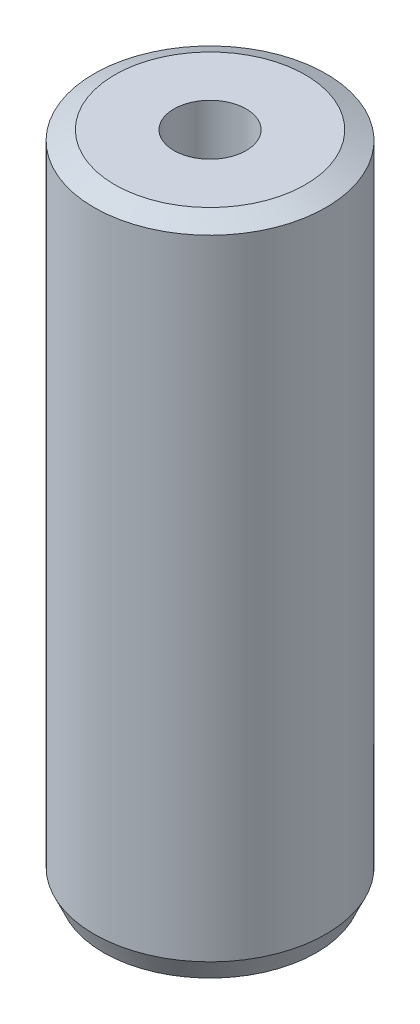
SolidWorks part; units mm, degrees
ref_plane "Front Plane" through (0, 0, 0) normal (0, 0, 1) x (1, 0, 0)
ref_plane "Top Plane" through (0, 0, 0) normal (0, 1, 0) x (1, 0, 0)
ref_plane "Right Plane" through (0, 0, 0) normal (1, 0, 0) x (0, 0, -1)
sketch "Sketch1" plane through (0, 0, 0) normal (0, 1, 0) x (1, 0, 0)
  circle A0 centre (0, 0) radius 47.5
  dimension "SHAFT_OD" = 95
extrude "Boss-Extrude1" add sketch "Sketch1" along normal blind 270.1124
sketch "Sketch2" plane through (0, 0, 0) normal (0, 1, 0) x (1, 0, 0)
  circle A0 centre (0, 0) radius 14.7958
  dimension "BORE_D" = 29.5915
extrude "Cut-Extrude1" cut sketch "Sketch2" along normal through all
chamfer "Chamfer1" distance 3.8536 angle 65.549 2 edges at (0, 270.1124, 47.5) (0, 0, 47.5) first distance on face at (0, 270.1124, 47.5) first distance on face at (0, 0, 14.7958)
